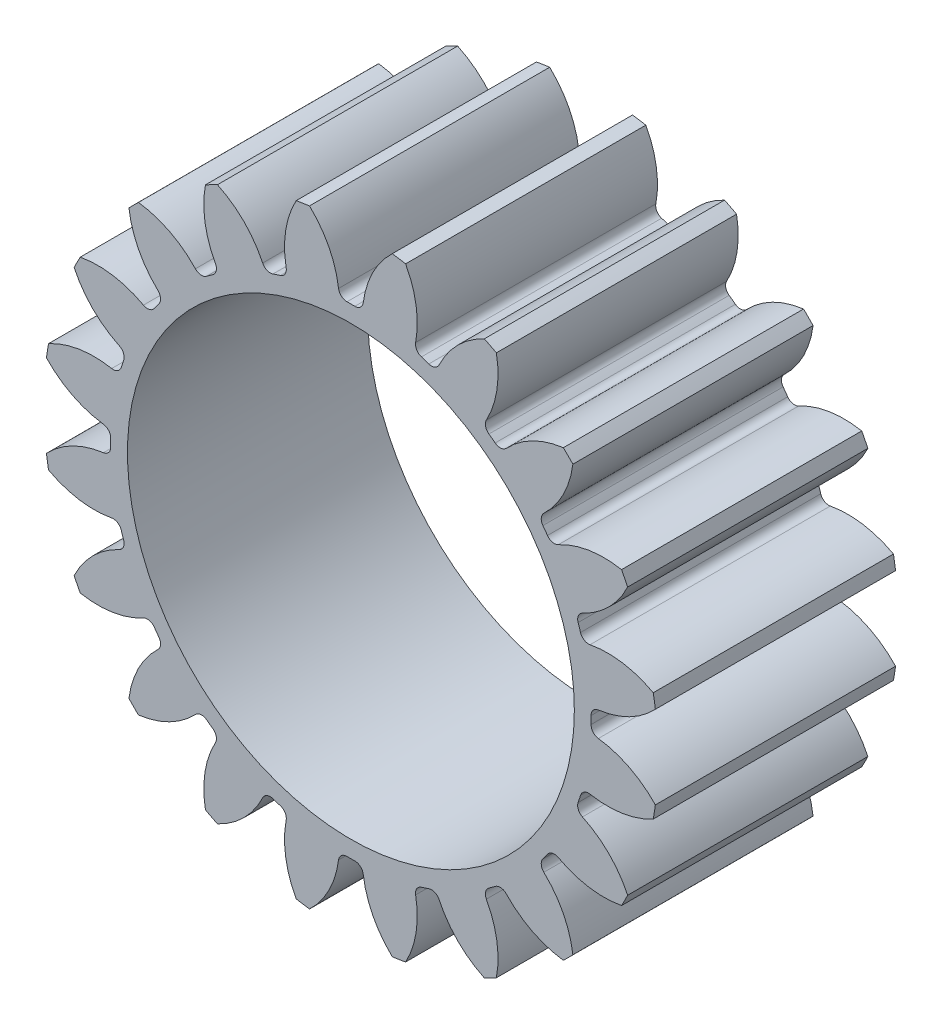
SolidWorks part; units mm, degrees
ref_plane "Front Plane" through (0, 0, 0) normal (0, 0, 1) x (1, 0, 0)
ref_plane "Top Plane" through (0, 0, 0) normal (0, 1, 0) x (1, 0, 0)
ref_plane "Right Plane" through (0, 0, 0) normal (1, 0, 0) x (0, 0, -1)
sketch "Sketch1" plane through (0, 0, 0) normal (0, 0, 1) x (1, 0, 0)
  circle A0 centre (0, 0) radius 5
  circle A1 centre (0, 0) radius 5.5
  circle A2 centre (0, 0) radius 4.3
  dimension "D1" = 10
  dimension "D2" = 0.5
  dimension "D3" = 1.2
extrude "Boss-Extrude1" add sketch "Sketch1" along normal mid plane 4.3 contours A1
sketch "Gear Profile" plane through (0, 0, 0) normal (0, 0, 1) x (1, 0, 0)
  line L0 (0, 0) -> (0, 5.5) construction
  line L1 (-0.3923, 4.9846) -> (0.3923, 4.9846) construction
  line L2 (-0.2089, 4.2949) -> (0, 0) construction
  line L3 (0, 4.2147) -> (-0.8769, 5.9356) construction
  line L4 (0, 0) -> (0.8604, 5.4323) construction
  line L5 (0.3923, 4.9846) -> (1.1672, 4.8618) construction
  circle A0 centre (0, 0) radius 5.5 construction
  arc A1 (-1.3974, 5.835) -> (-0.2089, 4.2949) centre (-1.908, 4.2123) cw
  arc A2 (1.3974, 5.835) -> (0.2089, 4.2949) centre (1.908, 4.2123) ccw
  circle A3 centre (0, 0) radius 4.3 construction
  arc A4 (0.2089, 4.2949) -> (-0.2089, 4.2949) centre (0, 0) ccw
  circle A5 centre (0, 0) radius 5 construction
  circle A6 centre (0, 0) radius 5.5 construction
  circle A7 centre (0, 0) radius 6
  arc A8 (1.3974, 5.835) -> (-1.3974, 5.835) centre (0, 0) ccw
  dimension "D2" = 27
  dimension "D3" = 9
  dimension "D1" = 0.5
extrude "Cut-Extrude1" cut sketch "Gear Profile" against normal through all both and the other way through all
fillet "Fillet1" radius 0.15 2 edges at (0.2089, 4.2949, 0) (-0.2089, 4.2949, 0)
ref_axis "Axis1" through (0, 0, -2.75) along (0, 0, 1)
pattern_circular "CirPattern1" count 20 over 360 about axis through (0, 0, -2.75) along (0, 0, 1) of "Fillet1", "Cut-Extrude1"
sketch "Sketch2" plane through (0, 0, 0) normal (0, 0, 1) x (1, 0, 0)
  circle A0 centre (0, 0) radius 4
  dimension "D1" = 8
extrude "Cut-Extrude2" cut sketch "Sketch2" against normal through all both and the other way through all
equation "\"Module\"= 0.5mm"
equation "\"Number of Teeth\"= 20"
equation "\"D1@Sketch1\"=\"Module\" * \"Number of Teeth\""
equation "\"D2@Sketch1\"=\"Module\""
equation "\"D3@Sketch1\"=\"Module\" * if( \"Module\"=>1.25,2.25,2.4)"
equation "\"Width\"= 4.3mm"
equation "\"D1@Boss-Extrude1\"=\"Width\""
equation "\"Pressure Angle\"= 27deg"
equation "\"D2@Gear Profile\"=\"Pressure Angle\""
equation "\"D3@Gear Profile\"=180 / \"Number of Teeth\""
equation "\"D1@Fillet1\"=0.3*\"Module\""
equation "\"D1@CirPattern1\"=\"Number of Teeth\""
equation "\"Hole Diammeter\" = 8"
equation "\"D1@Sketch2\"=\"Hole Diammeter\""
